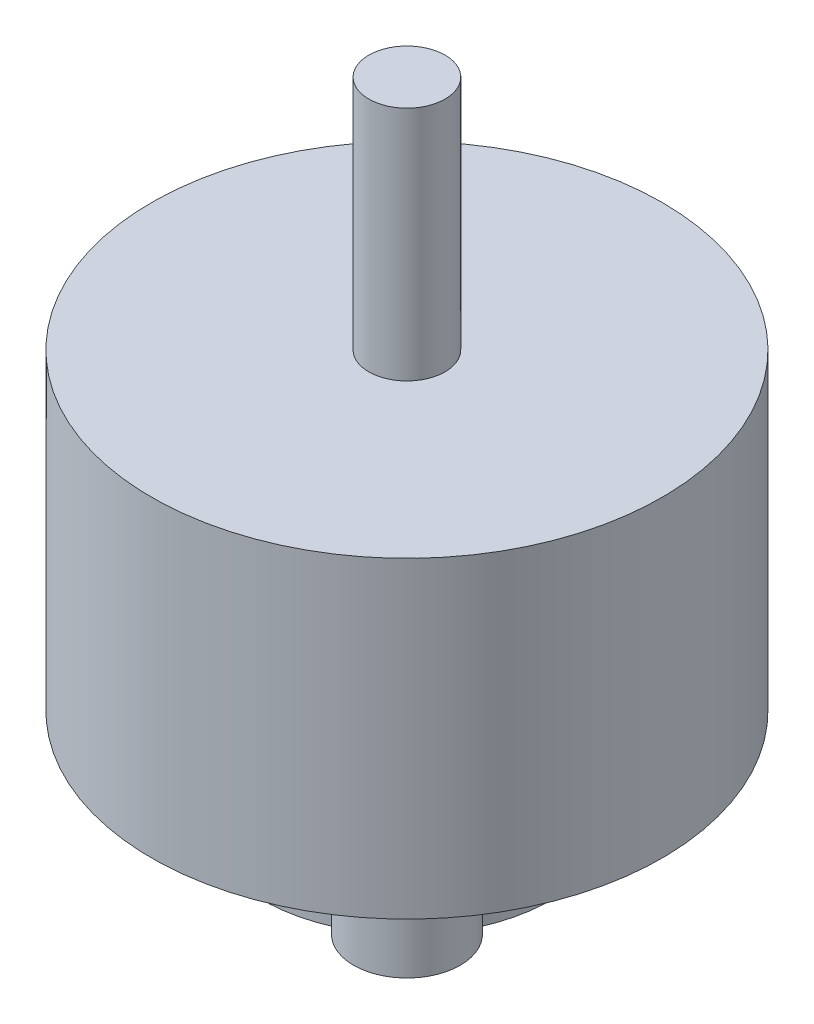
SolidWorks part; units mm, degrees
ref_plane "Plan de face" through (0, 0, 0) normal (0, 0, 1) x (1, 0, 0)
ref_plane "Plan de dessus" through (0, 0, 0) normal (0, 1, 0) x (1, 0, 0)
ref_plane "Plan de droite" through (0, 0, 0) normal (1, 0, 0) x (0, 0, -1)
sketch "Esquisse1" plane through (0, 0, 0) normal (0, 0, 1) x (1, 0, 0)
  line L0 (0, 0) -> (0, 42) construction
  line L1 (0, 0) -> (-9.5, 0)
  line L2 (-9.5, 0) -> (-9.5, 3.5)
  line L3 (-9.5, 3.5) -> (-7.5, 3.5)
  line L4 (-7.5, 3.5) -> (-6.75, 6)
  line L5 (-6.75, 6) -> (-16.75, 6)
  line L6 (-16.75, 6) -> (-16.75, 26.5)
  line L7 (-16.75, 26.5) -> (-2.5, 26.5)
  line L8 (-2.5, 26.5) -> (-2.5, 42)
  line L9 (-2.5, 42) -> (0, 42)
  line L10 (0, 0) -> (0, 42)
  dimension "D1" = 42
  dimension "D2" = 33.5
  dimension "D3" = 5
  dimension "D4" = 19
  dimension "D5" = 2
  dimension "D6" = 20.5
  dimension "D7" = 3.5
  dimension "D8" = 2.5
  dimension "D9" = 10
revolve "Révolution1" add sketch "Esquisse1" angle 360 about L0
sketch "Esquisse2" plane through (0, 0, 0) normal (0, -1, 0) x (-1, 0, 0)
  line L0 (0, 0) -> (0, -9.5) construction
  line L1 (6.7175, -6.7175) -> (0, 0) construction
  line L2 (0, 0) -> (6.7175, -6.7175) construction
  line L3 (0, 0) -> (-6.7175, -6.7175) construction
  circle A0 centre (6.7175, -6.7175) radius 3.5
  circle A1 centre (0, 0) radius 9.5 construction
  circle A2 centre (-6.7175, -6.7175) radius 3.5
  circle A3 centre (-6.7175, 6.7175) radius 3.5
  circle A4 centre (6.7175, 6.7175) radius 3.5
  dimension "D1" = 7
  dimension "D2" = 45
  dimension "D4" = 90
  dimension "D5" = 9.5
  dimension "D3" = 4
extrude "Boss.-Extru.1" add sketch "Esquisse2" against normal up to surface (3.5 mm away) up to face at (0, 3.5, -9.5)
hole_wizard "Dégagement M31" positions "Esquisse3D1" profile "Esquisse3" hole size "M3" standard "ISO" end condition up to next
sketch3d "Esquisse3D1"
  line L0 (0, 0, 0) -> (0, 0, 9.5) construction
  line L2 (-6.7175, 0, 6.7175) -> (0, 0, 0) construction
  line L4 (6.7175, 0, 6.7175) -> (0, 0, 0) construction
  line L6 (6.7175, 0, -6.7175) -> (0, 0, 0) construction
  line L8 (0, 0, 0) -> (-6.7175, 0, -6.7175) construction
  circle A2 centre (0, 0, 0) radius 9.5
  point P0 (-6.7175, 0, 6.7175)
  point P2 (6.7175, 0, 6.7175)
  point P4 (6.7175, 0, -6.7175)
  point P6 (-6.7175, 0, -6.7175)
  point P17 (0, 9.5, 0)
  point P40 (0, 0, 0)
  point P41 (0, 0, 0)
  point P42 (0, 0, 0)
  dimension "D1" = 19
  dimension "D2" = 45
  dimension "D3" = 45
  dimension "D4" = 90
  dimension "D5" = 90
sketch "Esquisse3" plane through (-6.7175, 0, 6.7175) normal (1, 0, 0) x (0, 0, -1)
  line L0 (0, 0) -> (0, 3.5)
  line L1 (0, 3.5) -> (1.7, 3.5)
  line L2 (1.7, 3.5) -> (1.7, 0)
  line L5 (1.7, 0) -> (0, 0)
  line L11 (0, -6.35) -> (0, 107.95) construction
  dimension "Diamètre du perçage jusqu'au prochain" = 3.4
  dimension "Profondeur du perçage jusqu'au prochain" = 3.5
